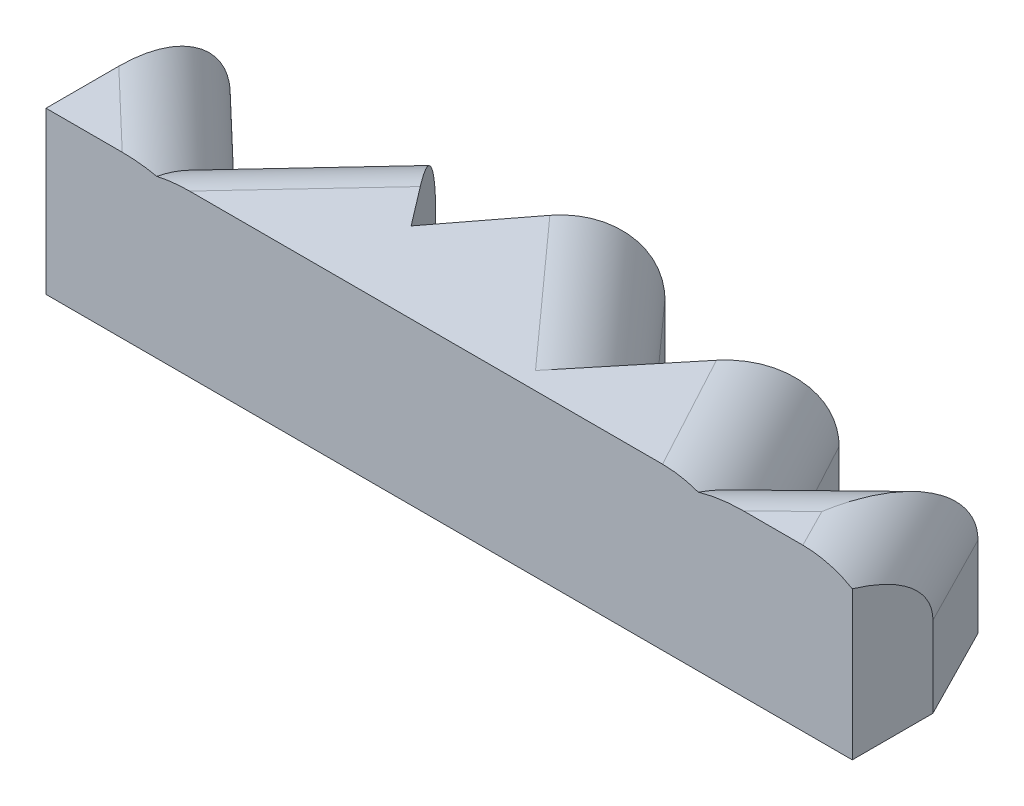
SolidWorks part; units mm, degrees
ref_plane "Front Plane" through (0, 0, 0) normal (0, 0, 1) x (1, 0, 0)
ref_plane "Top Plane" through (0, 0, 0) normal (0, 1, 0) x (1, 0, 0)
ref_plane "Right Plane" through (0, 0, 0) normal (1, 0, 0) x (0, 0, -1)
sketch "Sketch1" plane through (0, 129.5222, 0) normal (0, 1, 0) x (1, 0, 0)
  line L1 (-32.3481, -19.2763) -> (94.6519, -19.2763)
  line L2 (-32.3481, -19.2763) -> (-32.3481, -6.5763)
  line L3 (-32.3481, -6.5763) -> (94.6519, -6.5763)
  line L4 (94.6519, -19.2763) -> (94.6519, -6.5763)
  dimension "D1" = 12.7
  dimension "D2" = 127
extrude "Boss-Extrude1" add sketch "Sketch1" against normal up to surface (25.4 mm away)
sketch "Sketch2" plane through (0, 129.5222, 0) normal (0, 1, 0) x (1, 0, 0)
  line L0 (-32.3481, -6.5763) -> (-32.3481, 9.752)
  line L1 (-32.3481, 9.752) -> (-15.2528, -6.5763)
  line L2 (-15.2528, -6.5763) -> (0, 9.752)
  line L3 (0, 9.752) -> (12.4673, -6.5763)
  line L4 (12.4673, -6.5763) -> (29.799, 16.0596)
  line L5 (29.799, 16.0596) -> (50.1359, -6.5763)
  line L6 (50.1359, -6.5763) -> (63.5468, 9.752)
  line L7 (63.5468, 9.752) -> (72.3504, -6.5763)
  line L8 (72.3504, -6.5763) -> (87.273, 7.906)
  line L9 (87.273, 7.906) -> (94.6519, -6.5763)
  line L12 (94.6519, -6.5763) -> (-32.3481, -6.5763) construction
  line L13 (-32.3481, -6.5763) -> (-32.3481, -19.2763) construction
  line L15 (94.6519, -6.5763) -> (94.6519, -10.4966)
  line L16 (94.6519, -10.4966) -> (-32.3481, -10.4966)
  line L17 (-32.3481, -6.5763) -> (-32.3481, -10.4966)
extrude "Boss-Extrude2" add sketch "Sketch2" against normal up to surface (25.4 mm away)
fillet "Fillet2" radius 12.7 6 edges at (-23.8005, 129.5222, -1.5879) (-7.6264, 129.5222, -1.5879) (90.9624, 129.5222, -0.6649) (79.8117, 129.5222, -0.6649) (67.9486, 129.5222, -1.5879) (39.9674, 129.5222, -4.7417)
ref_plane "Print-base" through (0, 104.1222, 0) normal (0, -1, 0) x (-1, 0, 0)
